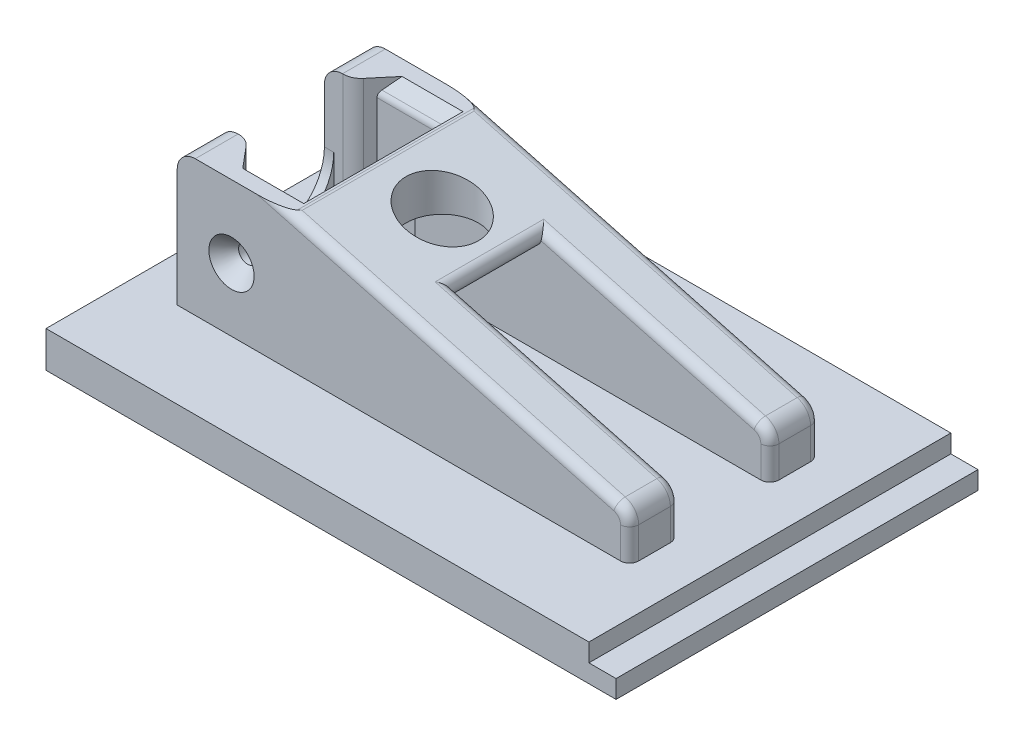
SolidWorks part; units mm, degrees
ref_plane "Ebene vorne" through (0, 0, 0) normal (0, 0, 1) x (1, 0, 0)
ref_plane "Ebene oben" through (0, 0, 0) normal (0, 1, 0) x (1, 0, 0)
ref_plane "Ebene rechts" through (0, 0, 0) normal (1, 0, 0) x (0, 0, -1)
sketch "Skizze1" plane through (0, 0, 0) normal (0, 1, 0) x (1, 0, 0)
  line L0 (0, 0) -> (60, 0)
  line L1 (-55, 0) -> (55, 0) construction
  line L2 (60, 0) -> (60, 40)
  line L3 (60, 40) -> (0, 40)
  line L4 (0, -55) -> (0, 55) construction
  line L5 (0, 40) -> (0, 0)
  line L6 (60, 20) -> (0, 20) construction
  line L7 (30, 0) -> (30, 40) construction
  dimension "D1" = 40
  dimension "D2" = 60
extrude "Aufsatz-Linear austragen1" add sketch "Skizze1" along normal blind 4
sketch "Skizze2" plane through (0, 4, 0) normal (0, 1, 0) x (1, 0, 0)
  line L0 (60, 20) -> (0, 20) construction
  line L1 (60, 0) -> (60, 40) construction
  line L2 (0, -2.2) -> (0, 2.2) construction
  line L3 (30, 20) -> (30, 0) construction
  line L4 (-2.2, 0) -> (2.2, 0) construction
  line L5 (30, 20) -> (30, 40) construction
  line L6 (60, 40) -> (0, 40) construction
  line L7 (55, 30.5) -> (55, 9.5)
  line L8 (55, 9.5) -> (5, 9.5)
  line L9 (5, 9.5) -> (5, 30.5)
  line L10 (55, 30.5) -> (5, 30.5)
  point P18 (5, 20)
  point P19 (55, 20)
  dimension "D1" = 50
  dimension "D2" = 21
  dimension "D3" = 5
extrude "Aufsatz-Linear austragen2" add sketch "Skizze2" along normal blind 15
sketch "Skizze3" plane through (0, 19, 0) normal (0, 1, 0) x (1, 0, 0)
  line L0 (55, 20) -> (5, 20) construction
  line L1 (55, 9.5) -> (55, 30.5) construction
  line L2 (5, 30.5) -> (5, 9.5) construction
  line L3 (30, 30.5) -> (30, 9.5) construction
  line L4 (55, 30.5) -> (5, 30.5) construction
  line L5 (5, 9.5) -> (55, 9.5) construction
  line L6 (15.7856, 12.7) -> (15.7856, 27.3)
  line L7 (15.7856, 12.7) -> (9.2856, 12.7)
  line L8 (9.2856, 12.7) -> (8, 14.2321)
  line L9 (8, 14.2321) -> (5, 14.2321)
  line L10 (5, 30.5) -> (5, 9.5) construction
  line L11 (8, 25.7679) -> (5, 25.7679)
  line L12 (9.2856, 27.3) -> (8, 25.7679)
  line L13 (15.7856, 27.3) -> (9.2856, 27.3)
  point P23 (15.7856, 20)
  dimension "D1" = 7.3
  dimension "D2" = 6.5
  dimension "D3" = 130
  dimension "D4" = 3
  dimension "D5" = 2
extrude "Schnitt-Linear austragen1" cut sketch "Skizze3" against normal blind 15 and the other way through all
fillet "Verrundung2" radius 2 2 edges at (8, 11.5, -25.7679) (8, 11.5, -14.2321)
sketch "Skizze10" plane through (0, 4, 0) normal (0, 1, 0) x (1, 0, 0)
  line L0 (5, 25.7679) -> (5, 14.2321)
  line L1 (5, 14.2321) -> (6.0337, 14.2321)
  line L2 (7.0674, 14.2321) -> (5, 14.2321) construction
  line L3 (6.0337, 14.2321) -> (6.0337, 25.7679)
  line L4 (5, 25.7679) -> (7.0674, 25.7679) construction
  line L5 (6.0337, 25.7679) -> (5, 25.7679)
extrude "Aufsatz-Linear austragen4" add sketch "Skizze10" along normal blind 7
sketch "Skizze12" plane through (5, 0, 0) normal (-1, 0, 0) x (0, 0, 1)
  line L0 (-25.7679, 11) -> (-14.2321, 11) construction
  circle A0 centre (-20, 11) radius 5.7679
extrude "Schnitt-Linear austragen4" cut sketch "Skizze12" against normal blind 3
chamfer "Fase6" distance 1.5 angle 45 1 edges at (15.7856, 19, -20)
fillet "Verrundung7" radius 1 1 edges at (15.7856, 17.5, -20)
fillet "Verrundung8" radius 2 2 edges at (5, 19, -11.866) (5, 19, -28.134)
chamfer "Fase7" distance 1.5 angle 45 2 edges at (13.2856, 19, -12.7) (13.2856, 19, -27.3)
fillet "Verrundung9" radius 1 2 edges at (12.5805, 17.5, -27.3) (12.5805, 17.5, -12.7)
sketch "Skizze15" plane through (0, 0, -30.5) normal (0, 0, -1) x (-1, 0, 0)
  line L0 (-5, 17) -> (-5, 4) construction
  line L1 (-60, 4) -> (0, 4) construction
  circle A0 centre (-11, 11) radius 1
  dimension "D1" = 2
  dimension "D2" = 7
  dimension "D3" = 6
extrude "Fixierbohrungen" cut sketch "Skizze15" against normal up to surface (21 mm away) up to face at (25.3172, 12.6828, -9.5)
sketch "Skizze16" plane through (0, 4, 0) normal (0, 1, 0) x (1, 0, 0)
  line L0 (15.7856, 27.3) -> (15.7856, 20.3)
  line L1 (15.7856, 27.3) -> (15.7856, 12.7) construction
  line L2 (15.7856, 20.3) -> (11.7856, 20.3)
  line L4 (9.2856, 27.3) -> (15.7856, 27.3) construction
  line L6 (11.7856, 20.3) -> (11.7856, 27.3)
  line L7 (15.7856, 27.3) -> (11.7856, 27.3)
  dimension "D1" = 7
  dimension "D2" = 4
extrude "Kabelschacht" cut sketch "Skizze16" against normal up to surface (4 mm away) up to face at (30, 0, -20)
chamfer "Fase_Bohrung" distance 1.5 angle 50 2 edges at (10, 11, -30.5) (10, 11, -9.5) first distance on face at (10, 11, -30.5) first distance on face at (10, 11, -9.5)
sketch "Skizze17" plane through (60, 0, 0) normal (1, 0, 0) x (0, 0, -1)
  line L0 (0, 0) -> (40, 0)
  line L1 (22, 0) -> (-22, 0) construction
  line L2 (40, 4) -> (40, 0) construction
  line L3 (40, 0) -> (40, 2)
  line L4 (40, 2) -> (0, 2)
  line L5 (0, 10.45) -> (0, -10.45) construction
  line L6 (0, 2) -> (0, 0)
  dimension "D1" = 2
extrude "Aufsatz-Linear austragen5" add sketch "Skizze17" along normal blind 3
sketch "Skizze19" plane through (15.7856, 0, 0) normal (-1, 0, 0) x (0, 0, 1)
  line L0 (-20, 17.0858) -> (-20, 0) construction
  line L1 (-12.7, 17.0858) -> (-27.3, 17.0858) construction
  line L2 (22, 0) -> (-22, 0) construction
  line L3 (-25, 4) -> (-15, 4)
  line L4 (-15, 4) -> (-15, 14)
  line L5 (-15, 14) -> (-25, 14)
  line L6 (-25, 4) -> (-25, 14)
  line L7 (-20.3, 4) -> (-12.7, 4) construction
  point P11 (-20, 14)
  point P12 (-20, 4)
  dimension "D1" = 5
  dimension "D2" = 10
  dimension "D3" = 0
extrude "Schnitt-Linear austragen5" cut sketch "Skizze19" against normal up to surface (39.2144 mm away) up to face at (55, 11.5, -20)
chamfer "Fase8" distance 10 angle 75 1 edges at (55, 19, -20) first distance on face at (55, 10.25, -20)
fillet "Verrundung16" radius 2 2 edges at (55, 9, -27.75) (55, 9, -12.25)
fillet "Verrundung17" radius 1 14 edges at (55, 5.7327, -15) (54.5867, 8.6829, -15) (55, 5.7327, -9.5) (54.5867, 8.6829, -9.5) (55, 5.7327, -30.5) (54.5867, 8.6829, -30.5) (55, 5.7327, -25) (54.5867, 8.6829, -25) (36.3397, 14, -20) (44.9287, 11.6986, -15) (35.5986, 14.1986, -9.5) (17.6795, 19, -20) (35.5986, 14.1986, -30.5) (44.9287, 11.6986, -25)
sketch "Skizze21" plane through (0, 14, 0) normal (0, -1, 0) x (1, 0, 0)
  line L0 (15.7856, -15) -> (15.7856, -25) construction
  line L1 (28.744, -15) -> (15.7856, -15) construction
  circle A0 centre (23.7856, -20) radius 4
  dimension "D1" = 8
  dimension "D2" = 8
  dimension "D3" = 5
extrude "Schnitt-Linear austragen6" cut sketch "Skizze21" against normal up to surface (3.3639 mm away) up to face at (38.4612, 13.4316, -20)
